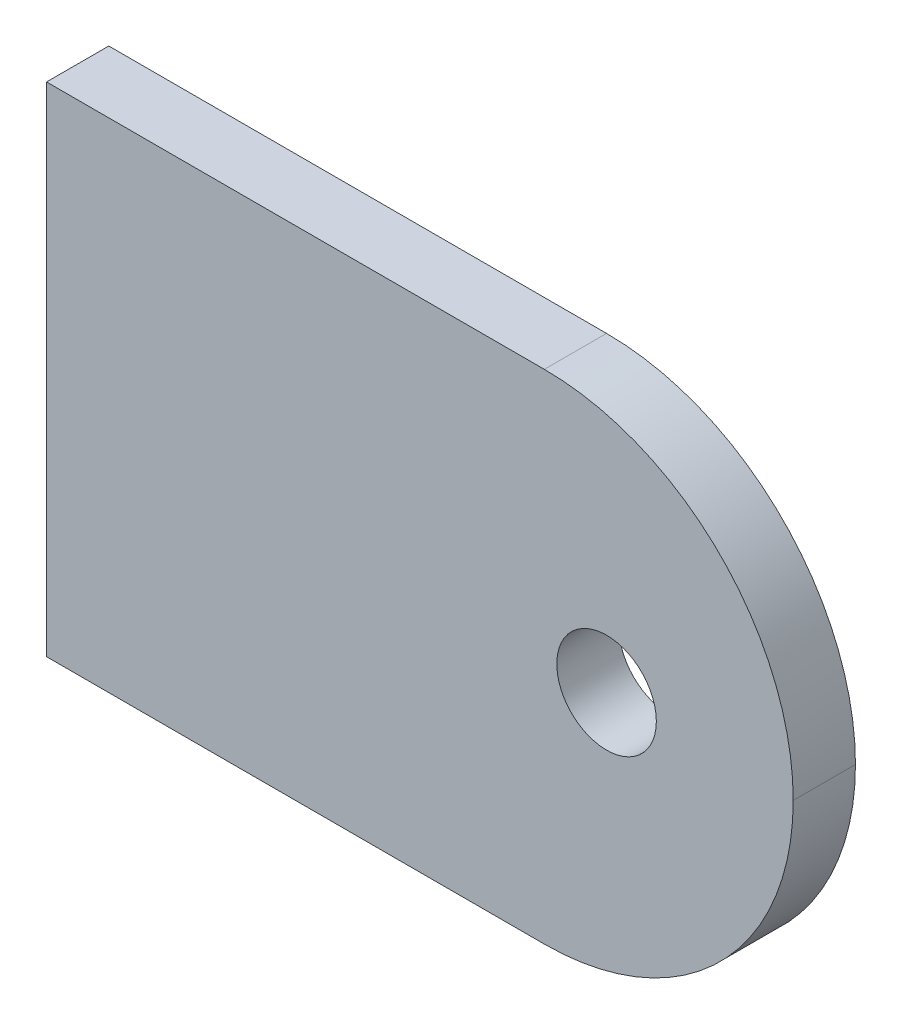
SolidWorks part; units mm, degrees
material "6061 Alloy"
ref_plane "Front Plane" through (0, 0, 0) normal (0, 0, 1) x (1, 0, 0)
ref_plane "Top Plane" through (0, 0, 0) normal (0, 1, 0) x (1, 0, 0)
ref_plane "Right Plane" through (0, 0, 0) normal (1, 0, 0) x (0, 0, -1)
sketch "Sketch1" plane through (0, 0, 0) normal (0, 0, 1) x (1, 0, 0)
  line L0 (0, 0) -> (0, 25.4)
  line L1 (0, 25.4) -> (38.1, 25.4)
  line L2 (38.1, 25.4) -> (38.1, 0)
  line L3 (38.1, 0) -> (0, 0)
  dimension "D1" = 38.1
  dimension "D2" = 25.4
extrude "Boss-Extrude1" add sketch "Sketch1" along normal blind 3.175
fillet "Fillet1" radius 12.7 2 edges at (38.1, 0, 1.5875) (38.1, 25.4, 1.5875)
sketch "Sketch2" plane through (0, 0, 3.175) normal (0, 0, 1) x (1, 0, 0)
  line L0 (25.4, 25.4) -> (0, 25.4) construction
  line L1 (0, 25.4) -> (0, 0) construction
  circle A0 centre (28.575, 12.7) radius 2.54
  dimension "D1" = 12.7
  dimension "D2" = 28.575
  dimension "D3" = 5.08
extrude "Cut-Extrude1" cut sketch "Sketch2" against normal through all
